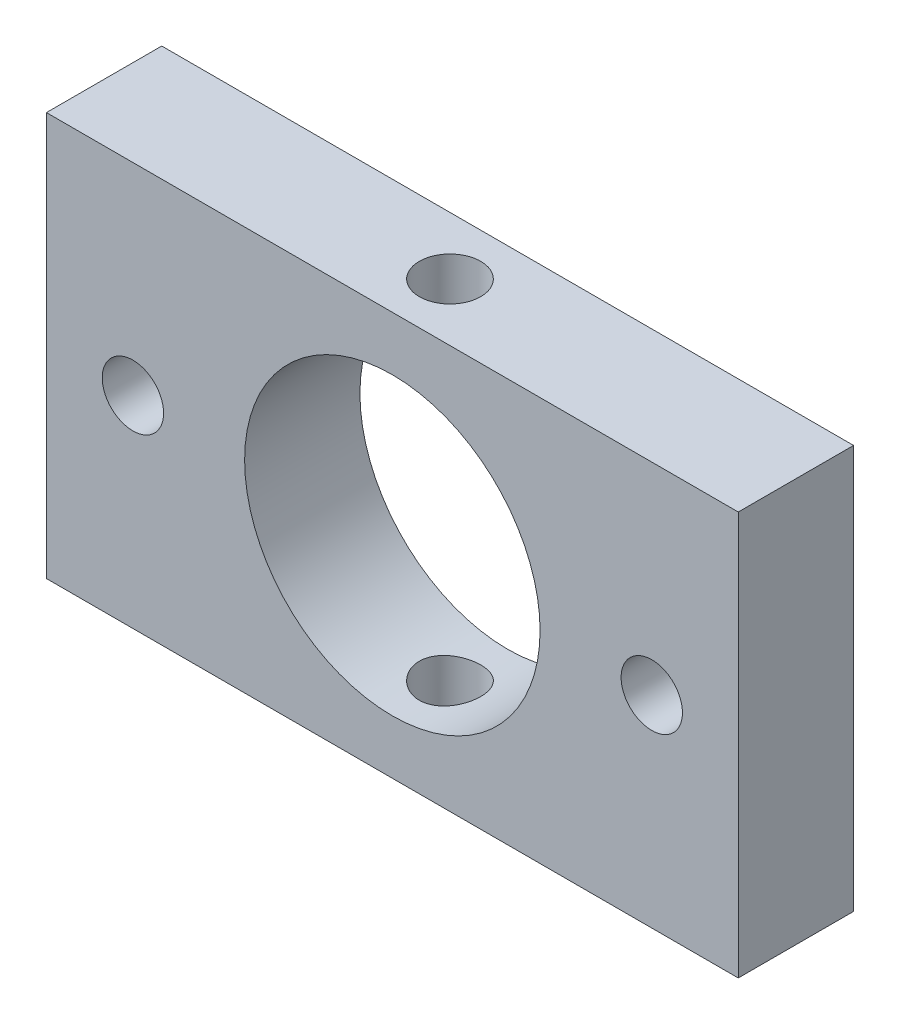
SolidWorks part; units mm, degrees
ref_plane "Front" through (0, 0, 0) normal (0, 0, 1) x (1, 0, 0)
ref_plane "Top" through (0, 0, 0) normal (0, 1, 0) x (1, 0, 0)
ref_plane "Right" through (0, 0, 0) normal (1, 0, 0) x (0, 0, -1)
sketch "Sketch1" plane through (0, 0, 0) normal (0, 0, 1) x (1, 0, 0)
  line L1 (-38.1, -22.225) -> (38.1, -22.225)
  line L2 (-38.1, -22.225) -> (-38.1, 22.225)
  line L3 (-38.1, 22.225) -> (38.1, 22.225)
  line L4 (38.1, -22.225) -> (38.1, 22.225)
  line L5 (-38.1, -22.225) -> (38.1, 22.225) construction
  line L6 (-38.1, 22.225) -> (38.1, -22.225) construction
  point P0 (0, 0)
  dimension "D1" = 44.45
  dimension "D2" = 76.2
extrude "Boss-Extrude1" add sketch "Sketch1" along normal blind 12.7
sketch "Sketch3" plane through (0, 0, 12.7) normal (0, 0, 1) x (1, 0, 0)
  line L1 (28.575, 0) -> (-28.575, 0) construction
  point P0 (0, 0)
  point P4 (0, 0)
  dimension "D2" = 57.15
hole_wizard "1-1/4 Clearance Hole1" positions "Sketch5" profile "Sketch4" hole size "1-1/4" standard "ANSI Inch" end condition through all
sketch "Sketch5" plane through (0, 0, 12.7) normal (0, 0, 1) x (1, 0, 0)
  point P0 (0, 0)
sketch "Sketch4" plane through (0, 0, 12.7) normal (1, 0, 0) x (0, -1, 0)
  line L0 (0, 0) -> (0, 12.7)
  line L1 (0, 12.7) -> (16.2712, 12.7)
  line L2 (16.2712, 12.7) -> (16.2712, 0)
  line L5 (16.2712, 0) -> (0, 0)
  line L11 (0, -6.35) -> (0, 107.95) construction
  dimension "Thru Hole Dia." = 32.5425
  dimension "Thru Hole Depth" = 12.7
hole_wizard "1/4 Clearance Hole1" positions "Sketch7" profile "Sketch6" hole size "1/4" standard "ANSI Inch" end condition through all
sketch "Sketch7" plane through (0, 0, 12.7) normal (0, 0, 1) x (1, 0, 0)
  point P0 (-28.575, 0)
  point P3 (28.575, 0)
sketch "Sketch6" plane through (-28.575, 0, 12.7) normal (1, 0, 0) x (0, -1, 0)
  line L0 (0, 0) -> (0, 12.7)
  line L1 (0, 12.7) -> (3.3782, 12.7)
  line L2 (3.3782, 12.7) -> (3.3782, 0)
  line L5 (3.3782, 0) -> (0, 0)
  line L11 (0, -6.35) -> (0, 107.95) construction
  dimension "Thru Hole Dia." = 6.7564
  dimension "Thru Hole Depth" = 12.7
sketch "Sketch8" plane through (0, 22.225, 0) normal (0, 1, 0) x (1, 0, 0)
  line L0 (0, 0) -> (0, -6.35) construction
  line L1 (38.1, 0) -> (-38.1, 0) construction
  line L2 (0, -6.35) -> (0, -12.7) construction
  line L3 (38.1, -12.7) -> (-38.1, -12.7) construction
hole_wizard "1/4 Clearance Hole2" positions "Sketch10" profile "Sketch9" hole size "1/4" standard "ANSI Inch" end condition through all
sketch "Sketch10" plane through (0, 22.225, 0) normal (0, 1, 0) x (1, 0, 0)
  point P0 (0, -6.35)
sketch "Sketch9" plane through (0, 22.225, 6.35) normal (1, 0, 0) x (0, 0, 1)
  line L0 (0, 0) -> (0, 44.45)
  line L1 (0, 44.45) -> (3.3782, 44.45)
  line L2 (3.3782, 44.45) -> (3.3782, 0)
  line L5 (3.3782, 0) -> (0, 0)
  line L11 (0, -6.35) -> (0, 107.95) construction
  dimension "Thru Hole Dia." = 6.7564
  dimension "Thru Hole Depth" = 44.45
